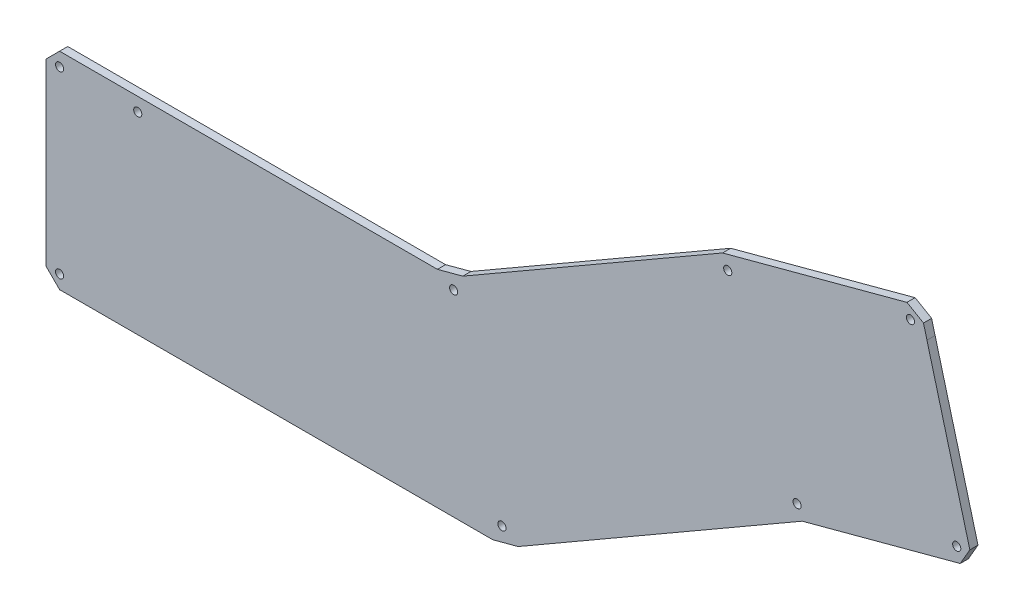
SolidWorks part; units mm, degrees
ref_plane "Plan de face" through (0, 0, 0) normal (0, 0, 1) x (1, 0, 0)
ref_plane "Plan de dessus" through (0, 0, 0) normal (0, 1, 0) x (1, 0, 0)
ref_plane "Plan de droite" through (0, 0, 0) normal (1, 0, 0) x (0, 0, -1)
sketch "Esquisse1" plane through (0, 0, 0) normal (0, 0, 1) x (1, 0, 0)
  line L0 (-73.9886, 18.0851) -> (-59.9886, 18.0851) construction
  line L1 (-73.9886, 37.0851) -> (-59.9886, 37.0851) construction
  line L2 (-73.9886, 37.0851) -> (-73.9886, 23.0851) construction
  line L3 (-73.9886, 23.0851) -> (-59.9886, 23.0851) construction
  line L4 (-59.9886, 37.0851) -> (-59.9886, 23.0851) construction
  line L5 (-73.9886, 18.0851) -> (-73.9886, 4.0851) construction
  line L6 (-73.9886, 4.0851) -> (-59.9886, 4.0851) construction
  line L7 (-59.9886, 18.0851) -> (-59.9886, 4.0851) construction
  line L8 (-73.9886, -0.9149) -> (-59.9886, -0.9149) construction
  line L9 (-73.9886, -0.9149) -> (-73.9886, -14.9149) construction
  line L10 (-73.9886, -14.9149) -> (-59.9886, -14.9149) construction
  line L11 (-59.9886, -0.9149) -> (-59.9886, -14.9149) construction
  line L12 (-73.9886, 37.0851) -> (-73.9886, 18.0851) construction
  line L13 (-54.9886, 18.0851) -> (-40.9886, 18.0851) construction
  line L14 (-54.9886, 37.0851) -> (-40.9886, 37.0851) construction
  line L15 (-54.9886, 37.0851) -> (-54.9886, 23.0851) construction
  line L16 (-54.9886, 23.0851) -> (-40.9886, 23.0851) construction
  line L17 (-40.9886, 37.0851) -> (-40.9886, 23.0851) construction
  line L18 (-54.9886, 18.0851) -> (-54.9886, 4.0851) construction
  line L19 (-54.9886, 4.0851) -> (-40.9886, 4.0851) construction
  line L20 (-40.9886, 18.0851) -> (-40.9886, 4.0851) construction
  line L21 (-54.9886, -0.9149) -> (-40.9886, -0.9149) construction
  line L22 (-54.9886, -0.9149) -> (-54.9886, -14.9149) construction
  line L23 (-54.9886, -14.9149) -> (-40.9886, -14.9149) construction
  line L24 (-40.9886, -0.9149) -> (-40.9886, -14.9149) construction
  line L25 (-54.9886, 37.0851) -> (-54.9886, 18.0851) construction
  line L26 (-35.9886, 18.0851) -> (-21.9886, 18.0851) construction
  line L27 (-35.9886, 37.0851) -> (-21.9886, 37.0851) construction
  line L28 (-35.9886, 37.0851) -> (-35.9886, 23.0851) construction
  line L29 (-35.9886, 23.0851) -> (-21.9886, 23.0851) construction
  line L30 (-21.9886, 37.0851) -> (-21.9886, 23.0851) construction
  line L31 (-35.9886, 18.0851) -> (-35.9886, 4.0851) construction
  line L32 (-35.9886, 4.0851) -> (-21.9886, 4.0851) construction
  line L33 (-21.9886, 18.0851) -> (-21.9886, 4.0851) construction
  line L34 (-35.9886, -0.9149) -> (-21.9886, -0.9149) construction
  line L35 (-35.9886, -0.9149) -> (-35.9886, -14.9149) construction
  line L36 (-35.9886, -14.9149) -> (-21.9886, -14.9149) construction
  line L37 (-21.9886, -0.9149) -> (-21.9886, -14.9149) construction
  line L38 (-35.9886, 37.0851) -> (-35.9886, 18.0851) construction
  line L39 (-16.9886, 18.0851) -> (-2.9886, 18.0851) construction
  line L40 (-16.9886, 37.0851) -> (-2.9886, 37.0851) construction
  line L41 (-16.9886, 37.0851) -> (-16.9886, 23.0851) construction
  line L42 (-16.9886, 23.0851) -> (-2.9886, 23.0851) construction
  line L43 (-2.9886, 37.0851) -> (-2.9886, 23.0851) construction
  line L44 (-16.9886, 18.0851) -> (-16.9886, 4.0851) construction
  line L45 (-16.9886, 4.0851) -> (-2.9886, 4.0851) construction
  line L46 (-2.9886, 18.0851) -> (-2.9886, 4.0851) construction
  line L47 (-16.9886, -0.9149) -> (-2.9886, -0.9149) construction
  line L48 (-16.9886, -0.9149) -> (-16.9886, -14.9149) construction
  line L49 (-16.9886, -14.9149) -> (-2.9886, -14.9149) construction
  line L50 (-2.9886, -0.9149) -> (-2.9886, -14.9149) construction
  line L51 (-16.9886, 37.0851) -> (-16.9886, 18.0851) construction
  line L52 (2.0114, 18.0851) -> (16.0114, 18.0851) construction
  line L53 (2.0114, 37.0851) -> (16.0114, 37.0851) construction
  line L54 (2.0114, 37.0851) -> (2.0114, 23.0851) construction
  line L55 (2.0114, 23.0851) -> (16.0114, 23.0851) construction
  line L56 (16.0114, 37.0851) -> (16.0114, 23.0851) construction
  line L57 (2.0114, 18.0851) -> (2.0114, 4.0851) construction
  line L58 (2.0114, 4.0851) -> (16.0114, 4.0851) construction
  line L59 (16.0114, 18.0851) -> (16.0114, 4.0851) construction
  line L60 (2.0114, -0.9149) -> (16.0114, -0.9149) construction
  line L61 (2.0114, -0.9149) -> (2.0114, -14.9149) construction
  line L62 (2.0114, -14.9149) -> (16.0114, -14.9149) construction
  line L63 (16.0114, -0.9149) -> (16.0114, -14.9149) construction
  line L64 (2.0114, 37.0851) -> (2.0114, 18.0851) construction
  line L65 (21.0114, 18.0851) -> (35.0114, 18.0851) construction
  line L66 (21.0114, 37.0851) -> (35.0114, 37.0851) construction
  line L67 (21.0114, 37.0851) -> (21.0114, 23.0851) construction
  line L68 (21.0114, 23.0851) -> (35.0114, 23.0851) construction
  line L69 (35.0114, 37.0851) -> (35.0114, 23.0851) construction
  line L70 (21.0114, 18.0851) -> (21.0114, 4.0851) construction
  line L71 (21.0114, 4.0851) -> (35.0114, 4.0851) construction
  line L72 (35.0114, 18.0851) -> (35.0114, 4.0851) construction
  line L73 (21.0114, -0.9149) -> (35.0114, -0.9149) construction
  line L74 (21.0114, -0.9149) -> (21.0114, -14.9149) construction
  line L75 (21.0114, -14.9149) -> (35.0114, -14.9149) construction
  line L76 (35.0114, -0.9149) -> (35.0114, -14.9149) construction
  line L77 (21.0114, 37.0851) -> (21.0114, 18.0851) construction
  line L78 (40.0114, 18.0851) -> (54.0114, 18.0851) construction
  line L79 (40.0114, 37.0851) -> (54.0114, 37.0851) construction
  line L80 (40.0114, 37.0851) -> (40.0114, 23.0851) construction
  line L81 (40.0114, 23.0851) -> (54.0114, 23.0851) construction
  line L82 (54.0114, 37.0851) -> (54.0114, 23.0851) construction
  line L83 (40.0114, 18.0851) -> (40.0114, 4.0851) construction
  line L84 (40.0114, 4.0851) -> (54.0114, 4.0851) construction
  line L85 (54.0114, 18.0851) -> (54.0114, 4.0851) construction
  line L86 (40.0114, -0.9149) -> (54.0114, -0.9149) construction
  line L87 (40.0114, -0.9149) -> (40.0114, -14.9149) construction
  line L88 (40.0114, -14.9149) -> (54.0114, -14.9149) construction
  line L89 (54.0114, -0.9149) -> (54.0114, -14.9149) construction
  line L90 (40.0114, 37.0851) -> (40.0114, 18.0851) construction
  line L91 (-73.9886, 18.0851) -> (-54.9886, 18.0851) construction
  line L92 (56.0114, 20.0851) -> (56.7532, 18.8002) construction
  line L93 (38.0114, 39.0851) -> (56.0114, 39.0851) construction
  line L94 (56.0114, 39.0851) -> (56.0114, 21.0851) construction
  line L95 (38.0114, 21.0851) -> (56.0114, 21.0851) construction
  line L96 (38.0114, 39.0851) -> (38.0114, 21.0851) construction
  line L97 (19.0114, 39.0851) -> (37.0114, 39.0851) construction
  line L98 (37.0114, 39.0851) -> (37.0114, 21.0851) construction
  line L99 (19.0114, 21.0851) -> (37.0114, 21.0851) construction
  line L100 (19.0114, 39.0851) -> (19.0114, 21.0851) construction
  line L101 (79.4363, 55.512) -> (88.4363, 39.9235) construction
  line L102 (88.4363, 39.9235) -> (72.8478, 30.9235) construction
  line L103 (63.8478, 46.512) -> (72.8478, 30.9235) construction
  line L104 (79.4363, 55.512) -> (63.8478, 46.512) construction
  line L105 (62.9818, 46.012) -> (71.9818, 30.4235) construction
  line L106 (71.9818, 30.4235) -> (56.3933, 21.4235) construction
  line L107 (47.3933, 37.012) -> (56.3933, 21.4235) construction
  line L108 (62.9818, 46.012) -> (47.3933, 37.012) construction
  line L109 (164.2542, 60.603) -> (148.6657, 51.603) construction
  line L110 (62.2497, 43.2799) -> (71.7497, 26.8254) construction
  line L111 (78.7042, 52.7799) -> (88.2042, 36.3254) construction
  line L112 (95.1587, 62.2799) -> (104.6587, 45.8254) construction
  line L113 (111.6132, 71.7799) -> (121.1132, 55.3254) construction
  line L114 (128.0677, 81.2799) -> (137.5677, 64.8254) construction
  line L115 (144.5221, 90.7799) -> (154.0221, 74.3254) construction
  line L116 (148.6657, 51.603) -> (157.6657, 36.0146) construction
  line L117 (69.1254, 3.371) -> (76.1254, -8.7534) construction
  line L118 (88.2497, -1.7534) -> (76.1254, -8.7534) construction
  line L119 (81.2497, 10.371) -> (88.2497, -1.7534) construction
  line L120 (81.2497, 10.371) -> (69.1254, 3.371) construction
  line L121 (59.6254, 19.8254) -> (66.6254, 7.7011) construction
  line L122 (78.7497, 14.7011) -> (66.6254, 7.7011) construction
  line L123 (71.7497, 26.8254) -> (78.7497, 14.7011) construction
  line L124 (50.1254, 36.2799) -> (57.1254, 24.1556) construction
  line L125 (69.2497, 31.1556) -> (57.1254, 24.1556) construction
  line L126 (62.2497, 43.2799) -> (69.2497, 31.1556) construction
  line L127 (62.2497, 43.2799) -> (50.1254, 36.2799) construction
  line L128 (71.7497, 26.8254) -> (59.6254, 19.8254) construction
  line L129 (85.5799, 12.871) -> (92.5799, 0.7466) construction
  line L130 (104.7042, 7.7466) -> (92.5799, 0.7466) construction
  line L131 (97.7042, 19.871) -> (104.7042, 7.7466) construction
  line L132 (97.7042, 19.871) -> (85.5799, 12.871) construction
  line L133 (76.0799, 29.3254) -> (83.0799, 17.2011) construction
  line L134 (95.2042, 24.2011) -> (83.0799, 17.2011) construction
  line L135 (88.2042, 36.3254) -> (95.2042, 24.2011) construction
  line L136 (66.5799, 45.7799) -> (73.5799, 33.6556) construction
  line L137 (85.7042, 40.6556) -> (73.5799, 33.6556) construction
  line L138 (78.7042, 52.7799) -> (85.7042, 40.6556) construction
  line L139 (78.7042, 52.7799) -> (66.5799, 45.7799) construction
  line L140 (88.2042, 36.3254) -> (76.0799, 29.3254) construction
  line L141 (102.0343, 22.371) -> (109.0343, 10.2466) construction
  line L142 (121.1587, 17.2466) -> (109.0343, 10.2466) construction
  line L143 (114.1587, 29.371) -> (121.1587, 17.2466) construction
  line L144 (114.1587, 29.371) -> (102.0343, 22.371) construction
  line L145 (92.5343, 38.8254) -> (99.5343, 26.7011) construction
  line L146 (111.6587, 33.7011) -> (99.5343, 26.7011) construction
  line L147 (104.6587, 45.8254) -> (111.6587, 33.7011) construction
  line L148 (83.0343, 55.2799) -> (90.0343, 43.1556) construction
  line L149 (102.1587, 50.1556) -> (90.0343, 43.1556) construction
  line L150 (95.1587, 62.2799) -> (102.1587, 50.1556) construction
  line L151 (95.1587, 62.2799) -> (83.0343, 55.2799) construction
  line L152 (104.6587, 45.8254) -> (92.5343, 38.8254) construction
  line L153 (118.4888, 31.871) -> (125.4888, 19.7466) construction
  line L154 (137.6132, 26.7466) -> (125.4888, 19.7466) construction
  line L155 (130.6132, 38.871) -> (137.6132, 26.7466) construction
  line L156 (130.6132, 38.871) -> (118.4888, 31.871) construction
  line L157 (108.9888, 48.3254) -> (115.9888, 36.2011) construction
  line L158 (128.1132, 43.2011) -> (115.9888, 36.2011) construction
  line L159 (121.1132, 55.3254) -> (128.1132, 43.2011) construction
  line L160 (99.4888, 64.7799) -> (106.4888, 52.6556) construction
  line L161 (118.6132, 59.6556) -> (106.4888, 52.6556) construction
  line L162 (111.6132, 71.7799) -> (118.6132, 59.6556) construction
  line L163 (111.6132, 71.7799) -> (99.4888, 64.7799) construction
  line L164 (121.1132, 55.3254) -> (108.9888, 48.3254) construction
  line L165 (134.9433, 41.371) -> (141.9433, 29.2466) construction
  line L166 (154.0677, 36.2466) -> (141.9433, 29.2466) construction
  line L167 (147.0677, 48.371) -> (154.0677, 36.2466) construction
  line L168 (147.0677, 48.371) -> (134.9433, 41.371) construction
  line L169 (125.4433, 57.8254) -> (132.4433, 45.7011) construction
  line L170 (144.5677, 52.7011) -> (132.4433, 45.7011) construction
  line L171 (137.5677, 64.8254) -> (144.5677, 52.7011) construction
  line L172 (115.9433, 74.2799) -> (122.9433, 62.1556) construction
  line L173 (135.0677, 69.1556) -> (122.9433, 62.1556) construction
  line L174 (128.0677, 81.2799) -> (135.0677, 69.1556) construction
  line L175 (128.0677, 81.2799) -> (115.9433, 74.2799) construction
  line L176 (137.5677, 64.8254) -> (125.4433, 57.8254) construction
  line L177 (151.3978, 50.871) -> (158.3978, 38.7466) construction
  line L178 (170.5221, 45.7466) -> (158.3978, 38.7466) construction
  line L179 (163.5221, 57.871) -> (170.5221, 45.7466) construction
  line L180 (163.5221, 57.871) -> (151.3978, 50.871) construction
  line L181 (141.8978, 67.3254) -> (148.8978, 55.2011) construction
  line L182 (161.0221, 62.2011) -> (148.8978, 55.2011) construction
  line L183 (154.0221, 74.3254) -> (161.0221, 62.2011) construction
  line L184 (132.3978, 83.7799) -> (139.3978, 71.6556) construction
  line L185 (151.5221, 78.6556) -> (139.3978, 71.6556) construction
  line L186 (144.5221, 90.7799) -> (151.5221, 78.6556) construction
  line L187 (144.5221, 90.7799) -> (132.3978, 83.7799) construction
  line L188 (154.0221, 74.3254) -> (141.8978, 67.3254) construction
  line L189 (173.2542, 45.0146) -> (157.6657, 36.0146) construction
  line L190 (164.2542, 60.603) -> (173.2542, 45.0146) construction
  line L191 (178.3169, 34.0986) -> (169.0534, 56.4627) construction
  line L192 (169.5193, 62.7839) -> (174.1781, 45.3972) construction
  line L193 (174.1781, 45.3972) -> (191.5647, 50.056) construction
  line L194 (186.906, 67.4426) -> (191.5647, 50.056) construction
  line L195 (162.1337, 98.0749) -> (167.0513, 79.7223) construction
  line L196 (169.5193, 62.7839) -> (186.906, 67.4426) construction
  line L197 (167.0513, 79.7223) -> (180.5742, 83.3457) construction
  line L198 (162.1337, 98.0749) -> (175.6567, 101.6983) construction
  line L199 (162.1337, 98.0749) -> (165.7572, 84.5519) construction
  line L200 (165.7572, 84.5519) -> (179.2801, 88.1754) construction
  line L201 (175.6567, 101.6983) -> (179.2801, 88.1754) construction
  line L202 (167.0513, 79.7223) -> (170.6747, 66.1993) construction
  line L203 (170.6747, 66.1993) -> (184.1977, 69.8228) construction
  line L204 (180.5742, 83.3457) -> (184.1977, 69.8228) construction
  line L205 (171.9688, 61.3697) -> (185.4918, 64.9932) construction
  line L206 (171.9688, 61.3697) -> (175.5923, 47.8467) construction
  line L207 (175.5923, 47.8467) -> (189.1152, 51.4702) construction
  line L208 (185.4918, 64.9932) -> (189.1152, 51.4702) construction
  line L209 (185.4038, 84.6398) -> (198.9268, 88.2633) construction
  line L210 (180.4863, 102.9924) -> (194.0092, 106.6159) construction
  line L211 (180.4863, 102.9924) -> (184.1097, 89.4695) construction
  line L212 (184.1097, 89.4695) -> (197.6327, 93.0929) construction
  line L213 (194.0092, 106.6159) -> (197.6327, 93.0929) construction
  line L214 (185.4038, 84.6398) -> (189.0273, 71.1169) construction
  line L215 (189.0273, 71.1169) -> (202.5503, 74.7403) construction
  line L216 (198.9268, 88.2633) -> (202.5503, 74.7403) construction
  line L217 (190.3214, 66.2873) -> (203.8444, 69.9107) construction
  line L218 (190.3214, 66.2873) -> (193.9449, 52.7643) construction
  line L219 (193.9449, 52.7643) -> (207.4678, 56.3878) construction
  line L220 (203.8444, 69.9107) -> (207.4678, 56.3878) construction
  line L221 (187.8719, 67.7015) -> (192.5307, 50.3148) construction
  line L222 (192.5307, 50.3148) -> (209.9173, 54.9735) construction
  line L223 (205.2586, 72.3602) -> (209.9173, 54.9735) construction
  line L224 (180.4863, 102.9924) -> (185.4038, 84.6398) construction
  line L225 (187.8719, 67.7015) -> (205.2586, 72.3602) construction
  line L226 (203.7564, 89.5574) -> (217.2794, 93.1809) construction
  line L227 (198.8389, 107.91) -> (212.3618, 111.5335) construction
  line L228 (198.8389, 107.91) -> (202.4623, 94.387) construction
  line L229 (202.4623, 94.387) -> (215.9853, 98.0105) construction
  line L230 (212.3618, 111.5335) -> (215.9853, 98.0105) construction
  line L231 (203.7564, 89.5574) -> (207.3799, 76.0344) construction
  line L232 (207.3799, 76.0344) -> (220.9029, 79.6579) construction
  line L233 (217.2794, 93.1809) -> (220.9029, 79.6579) construction
  line L234 (208.674, 71.2048) -> (222.197, 74.8283) construction
  line L235 (208.674, 71.2048) -> (212.2975, 57.6819) construction
  line L236 (212.2975, 57.6819) -> (225.8204, 61.3053) construction
  line L237 (222.197, 74.8283) -> (225.8204, 61.3053) construction
  line L238 (206.2245, 72.619) -> (210.8833, 55.2324) construction
  line L239 (210.8833, 55.2324) -> (228.2699, 59.8911) construction
  line L240 (223.6112, 77.2778) -> (228.2699, 59.8911) construction
  line L241 (198.8389, 107.91) -> (203.7564, 89.5574) construction
  line L242 (206.2245, 72.619) -> (223.6112, 77.2778) construction
  line L243 (167.0513, 79.7223) -> (185.4038, 84.6398) construction
  line L244 (38.0114, 20.0851) -> (56.0114, 20.0851) construction
  line L245 (56.0114, 20.0851) -> (56.0114, 2.0851) construction
  line L246 (38.0114, 2.0851) -> (56.0114, 2.0851) construction
  line L247 (38.0114, 20.0851) -> (38.0114, 2.0851) construction
  line L248 (72.4818, 29.5575) -> (56.8933, 20.5575) construction
  line L249 (56.8933, 20.5575) -> (65.8933, 4.969) construction
  line L250 (81.4818, 13.969) -> (65.8933, 4.969) construction
  line L251 (72.4818, 29.5575) -> (81.4818, 13.969) construction
  line L252 (56.8933, 20.5575) -> (57.6111, 19.3142) construction
  line L253 (164.6018, 81.1365) -> (169.2605, 63.7498) construction
  line L254 (169.2605, 63.7498) -> (186.6472, 68.4086) construction
  line L255 (181.9884, 85.7952) -> (186.6472, 68.4086) construction
  line L256 (164.6018, 81.1365) -> (181.9884, 85.7952) construction
  line L257 (154.7542, 77.0575) -> (163.7542, 61.469) construction
  line L258 (163.7542, 61.469) -> (148.1657, 52.469) construction
  line L259 (139.1657, 68.0575) -> (148.1657, 52.469) construction
  line L260 (154.7542, 77.0575) -> (139.1657, 68.0575) construction
  line L261 (196.3894, 109.3242) -> (213.776, 113.983) construction
  line L262 (-94.7538, 35.7952) -> (-76.7538, 35.7952) construction
  line L263 (-94.7538, 35.7952) -> (-94.7538, 2.7952) construction
  line L264 (-94.7538, 2.7952) -> (-76.7538, 2.7952) construction
  line L265 (-76.7538, 35.7952) -> (-76.7538, 2.7952) construction
  line L266 (213.776, 113.983) -> (218.4348, 96.5963) construction
  line L267 (201.0481, 91.9375) -> (218.4348, 96.5963) construction
  line L268 (196.3894, 109.3242) -> (201.0481, 91.9375) construction
  line L269 (-75.9886, -16.9149) -> (-57.9886, -16.9149) construction
  line L270 (-57.9886, 1.0851) -> (-57.9886, -16.9149) construction
  line L271 (-75.9886, 1.0851) -> (-57.9886, 1.0851) construction
  line L272 (-75.9886, 1.0851) -> (-75.9886, -16.9149) construction
  line L273 (38.0114, -16.9149) -> (56.0114, -16.9149) construction
  line L274 (56.0114, 1.0851) -> (56.0114, -16.9149) construction
  line L275 (38.0114, 1.0851) -> (56.0114, 1.0851) construction
  line L276 (38.0114, 1.0851) -> (38.0114, -16.9149) construction
  line L277 (-75.9886, 39.0851) -> (-57.9886, 39.0851) construction
  line L278 (-57.9886, 39.0851) -> (-57.9886, 21.0851) construction
  line L279 (-75.9886, 21.0851) -> (-57.9886, 21.0851) construction
  line L280 (-75.9886, 39.0851) -> (-75.9886, 21.0851) construction
  line L281 (145.2542, 93.512) -> (129.6657, 84.512) construction
  line L282 (129.6657, 84.512) -> (138.6657, 68.9235) construction
  line L283 (154.2542, 77.9235) -> (138.6657, 68.9235) construction
  line L284 (145.2542, 93.512) -> (154.2542, 77.9235) construction
  line L285 (223.4353, 116.5711) -> (228.0941, 99.1845) construction
  line L286 (148.2159, 106.7689) -> (211.1879, 123.6422) construction
  line L287 (177.5508, 35.9482) -> (235.6877, 51.5259) construction
  line L288 (177.5508, 35.9482) -> (72.9989, -24.4149) construction
  line L289 (-95.7538, -26.9149) -> (63.6687, -26.9149) construction
  line L290 (-100.7538, 35.7952) -> (-100.7538, -21.9149) construction
  line L291 (-75.9886, 49.0851) -> (43.3046, 49.0851) construction
  line L292 (148.2159, 106.7689) -> (52.6347, 51.5851) construction
  line L293 (-75.9886, 49.0851) -> (-57.9886, 49.0851) construction
  line L294 (140.2542, 102.1722) -> (124.6657, 93.1722) construction
  line L295 (193.8012, 118.9835) -> (211.1879, 123.6422) construction
  line L296 (213.4714, 45.5731) -> (230.8581, 50.2318) construction
  line L297 (38.0114, -26.9149) -> (38.0114, -85.4624) construction
  line L298 (178.2542, 36.3543) -> (162.6657, 27.3543) construction
  line L299 (38.0114, -26.9149) -> (56.0114, -26.9149) construction
  line L300 (-100.7538, 2.7952) -> (-100.7538, -38.0419) construction
  line L301 (-100.7538, 35.7952) -> (-100.7538, 2.7952) construction
  line L302 (-75.9886, 49.0851) -> (-95.7538, 49.0851) construction
  line L303 (-100.7538, 44.0851) -> (-100.7538, 35.7952) construction
  line L304 (211.1879, 123.6422) -> (216.0732, 124.9512) construction
  line L305 (222.1691, 121.4083) -> (223.4353, 116.5711) construction
  line L306 (228.0941, 99.1845) -> (239.2233, 57.6497) construction
  line L307 (216.0732, 124.9512) -> (222.1691, 121.4083) construction
  line L308 (235.6877, 51.5259) -> (239.2233, 57.6497) construction
  line L309 (63.6687, -26.9149) -> (72.9989, -24.4149) construction
  line L310 (52.6347, 51.5851) -> (43.3046, 49.0851) construction
  line L311 (-95.7538, 49.0851) -> (-100.7538, 44.0851) construction
  line L312 (-100.7538, -21.9149) -> (-95.7538, -26.9149) construction
  line L313 (-95.7538, 49.0851) -> (-95.7538, 44.0851) construction
  line L314 (-95.7538, 44.0851) -> (-100.7538, 44.0851) construction
  line L315 (-95.7538, -26.9149) -> (-95.7538, -21.9149) construction
  line L316 (68.3338, -25.6649) -> (67.0397, -20.8353) construction
  line L317 (47.9697, 50.3351) -> (49.2637, 45.5055) construction
  line L318 (177.5508, 35.9482) -> (175.6374, 40.5676) construction
  line L319 (148.2159, 106.7689) -> (150.1293, 102.1495) construction
  line L320 (239.2233, 57.6497) -> (234.3936, 56.3556) construction
  line L321 (216.0732, 124.9512) -> (217.3634, 120.1206) construction
  line L322 (-75.9886, 51.0851) -> (43.0413, 51.0851) construction
  line L323 (51.8627, 53.4488) -> (43.0413, 51.0851) construction
  line L324 (147.4439, 108.6326) -> (51.8627, 53.4488) construction
  line L325 (147.4439, 108.6326) -> (210.6702, 125.5741) construction
  line L326 (210.6702, 125.5741) -> (216.3591, 127.0984) construction
  line L327 (216.3591, 127.0984) -> (223.8932, 122.7195) construction
  line L328 (223.8932, 122.7195) -> (225.3687, 117.0832) construction
  line L329 (225.3687, 117.0832) -> (230.0259, 99.7021) construction
  line L330 (230.0259, 99.7021) -> (241.3695, 57.3671) construction
  line L331 (237.0056, 49.8085) -> (241.3695, 57.3671) construction
  line L332 (178.3228, 34.0845) -> (237.0056, 49.8085) construction
  line L333 (178.3228, 34.0845) -> (73.7708, -26.2786) construction
  line L334 (63.932, -28.9149) -> (73.7708, -26.2786) construction
  line L335 (-96.5822, -28.9149) -> (63.932, -28.9149) construction
  line L336 (-102.7538, -22.7433) -> (-96.5822, -28.9149) construction
  line L337 (-102.7538, 35.7952) -> (-102.7538, -22.7433) construction
  line L338 (-102.7538, 44.9135) -> (-102.7538, 35.7952) construction
  line L339 (-96.5822, 51.0851) -> (-102.7538, 44.9135) construction
  line L340 (-75.9886, 51.0851) -> (-76.7538, 51.0851) construction
  line L341 (2.0114, 40.0851) -> (52.7161, 40.0851) construction
  line L342 (151.6898, 98.3823) -> (50.7161, 40.0851) construction
  line L343 (-100.7538, 35.7952) -> (-100.7538, -17.9149) construction
  line L344 (-100.7538, -17.9149) -> (66.2572, -17.9149) construction
  line L345 (174.0769, 44.3349) -> (66.2572, -17.9149) construction
  line L346 (174.0769, 44.3349) -> (229.4947, 59.184) construction
  line L347 (214.4832, 115.2077) -> (229.4947, 59.184) construction
  line L348 (151.6898, 98.3823) -> (214.4832, 115.2077) construction
  line L349 (225.0947, 75.6047) -> (228.7182, 62.0818) construction
  line L350 (176.3687, 44.949) -> (189.8917, 48.5724) construction
  line L351 (89.7497, -4.3515) -> (77.6254, -11.3515) construction
  line L352 (-54.9886, -17.9149) -> (-40.9886, -17.9149) construction
  line L353 (-100.7538, 35.7952) -> (-100.7538, 2.7952) construction
  line L354 (2.0114, 40.0851) -> (16.0114, 40.0851) construction
  line L355 (77.2042, 55.378) -> (65.0799, 48.378) construction
  line L356 (179.7098, 105.8902) -> (193.2328, 109.5137) construction
  line L357 (2.0114, 40.0851) -> (-100.7538, 40.0851) construction
  line L358 (-95.7538, 44.0851) -> (-60.6491, 44.0851) construction
  line L359 (-100.7538, 35.7952) -> (-100.7538, 40.0851) construction
  line L360 (-75.9886, 49.5851) -> (43.2388, 49.5851) construction
  line L361 (52.4417, 52.051) -> (43.2388, 49.5851) construction
  line L362 (-76.7538, 51.0851) -> (-96.5822, 51.0851) construction
  line L363 (-66.9886, 37.0851) -> (-66.9886, 51.0851) construction
  line L364 (-75.9886, 51.0851) -> (-96.5822, 51.0851) construction
  line L365 (148.0229, 107.2348) -> (52.4417, 52.051) construction
  line L366 (-76.7538, 39.0851) -> (-97.0101, 39.0851) construction
  line L367 (-76.7538, 39.0851) -> (-76.7538, 1.0851) construction
  line L368 (-76.7538, 1.0851) -> (-97.0101, 1.0851) construction
  line L369 (-97.0101, 39.0851) -> (-97.0101, 1.0851) construction
  line L370 (148.0229, 107.2348) -> (211.0584, 124.1252) construction
  line L371 (211.0584, 124.1252) -> (216.1447, 125.488) construction
  line L372 (216.1447, 125.488) -> (222.6001, 121.7361) construction
  line L373 (222.6001, 121.7361) -> (223.9186, 116.6992) construction
  line L374 (223.9186, 116.6992) -> (228.577, 99.3139) construction
  line L375 (228.577, 99.3139) -> (239.7598, 57.579) construction
  line L376 (236.0172, 51.0966) -> (239.7598, 57.579) construction
  line L377 (177.7438, 35.4823) -> (236.0172, 51.0966) construction
  line L378 (177.7438, 35.4823) -> (73.1918, -24.8808) construction
  line L379 (63.7346, -27.4149) -> (73.1918, -24.8808) construction
  line L380 (-95.9609, -27.4149) -> (63.7346, -27.4149) construction
  line L381 (-101.2538, -22.122) -> (-95.9609, -27.4149) construction
  line L382 (-101.2538, 35.7952) -> (-101.2538, -22.122) construction
  line L383 (-101.2538, 44.2922) -> (-101.2538, 35.7952) construction
  line L384 (-95.9609, 49.5851) -> (-101.2538, 44.2922) construction
  line L385 (-76.7538, 49.5851) -> (-95.9609, 49.5851) construction
  line L386 (-75.9886, 49.5851) -> (-76.7538, 49.5851) construction
  line L387 (-76.7538, 49.0851) -> (-95.7538, 49.0851)
  line L388 (-95.7538, 49.0851) -> (-100.7538, 44.0851)
  line L389 (-100.7538, 44.0851) -> (-100.7538, 35.7952)
  line L390 (-100.7538, 35.7952) -> (-100.7538, -21.9149)
  line L391 (-100.7538, -21.9149) -> (-95.7538, -26.9149)
  line L392 (-95.7538, -26.9149) -> (63.6687, -26.9149)
  line L393 (63.6687, -26.9149) -> (72.9989, -24.4149)
  line L394 (177.5508, 35.9482) -> (72.9989, -24.4149)
  line L395 (177.5508, 35.9482) -> (235.6877, 51.5259)
  line L396 (235.6877, 51.5259) -> (239.2233, 57.6497)
  line L397 (228.0941, 99.1845) -> (239.2233, 57.6497)
  line L398 (223.4353, 116.5711) -> (228.0941, 99.1845)
  line L399 (222.1691, 121.4083) -> (223.4353, 116.5711)
  line L400 (216.0732, 124.9512) -> (222.1691, 121.4083)
  line L401 (211.1879, 123.6422) -> (216.0732, 124.9512)
  line L402 (148.2159, 106.7689) -> (211.1879, 123.6422)
  line L403 (148.2159, 106.7689) -> (52.6347, 51.5851)
  line L404 (52.6347, 51.5851) -> (43.3046, 49.0851)
  line L405 (-75.9886, 49.0851) -> (43.3046, 49.0851)
  line L406 (-75.9886, 49.0851) -> (-76.7538, 49.0851)
  circle A0 centre (-95.7538, 44.0851) radius 1.5
  circle A1 centre (-95.7538, -21.9149) radius 1.5
  circle A2 centre (67.0397, -20.8353) radius 1.5
  circle A3 centre (49.2637, 45.5055) radius 1.5
  circle A4 centre (175.6374, 40.5676) radius 1.5
  circle A5 centre (150.1293, 102.1495) radius 1.5
  circle A6 centre (234.3936, 56.3556) radius 1.5
  circle A7 centre (217.3634, 120.1206) radius 1.5
  circle A8 centre (-66.9886, 44.0851) radius 1.5
  point P304 (48.3046, 49.0851)
  point P305 (240.5174, 52.82)
  point P308 (68.6687, -26.9149)
  point P309 (-100.7538, -26.9149)
  point P311 (-100.7538, 49.0851)
  point P312 (220.9029, 126.2453)
  dimension "D32" = 3
  dimension "D33" = 5
  dimension "D40" = 5
  dimension "D41" = 5
  dimension "D42" = 5
  dimension "D43" = 5
  dimension "D44" = 2
  dimension "D53" = 1.5
  dimension "D1" = 14
  dimension "D2" = 14
  dimension "D4" = 19
  dimension "D6" = 19
  dimension "D7" = 30
  dimension "D10" = 1
  dimension "D11" = 2
  dimension "D13" = 0.5
  dimension "D15" = 2
  dimension "D12" = 7.5
  dimension "D14" = 19
  dimension "D18" = 2
  dimension "D20" = 18
  dimension "D21" = 33
  dimension "D22" = 2
  dimension "D8" = 2
  dimension "D9" = 2
  dimension "D16" = 2
  dimension "D19" = 2
  dimension "D23" = 2
  dimension "D24" = 10
  dimension "D25" = 10
  dimension "D26" = 10
  dimension "D27" = 10
  dimension "D28" = 10
  dimension "D29" = 6
  dimension "D30" = 10
  dimension "D31" = 10
  dimension "D45" = 3
  dimension "D46" = 3
  dimension "D47" = 6
  dimension "D48" = 3
  dimension "D49" = 3
  dimension "D50" = 3
  dimension "D51" = 3
  dimension "D52" = 3
  dimension "D54" = 0.5
  dimension "D3" = 3
  dimension "D5" = 7
  dimension "D17" = 3
extrude "Boss.-Extru.1" add sketch "Esquisse1" along normal blind 3
